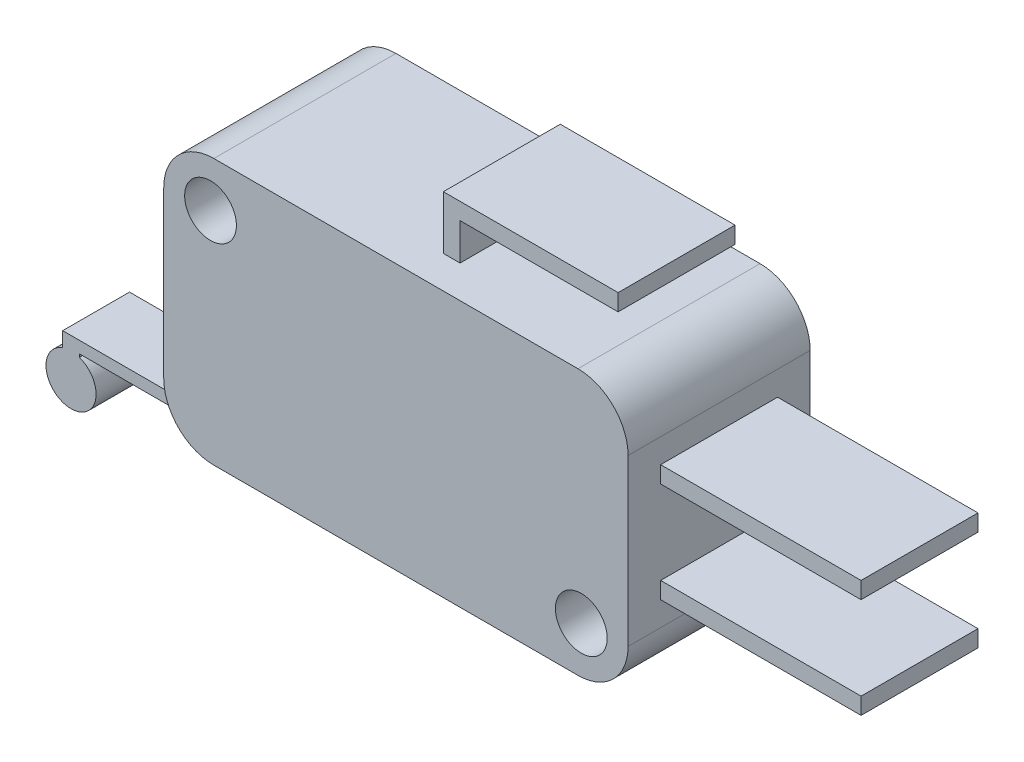
SolidWorks part; units mm, degrees
ref_plane "Front Plane" through (0, 0, 0) normal (0, 0, 1) x (1, 0, 0)
ref_plane "Top Plane" through (0, 0, 0) normal (0, 1, 0) x (1, 0, 0)
ref_plane "Right Plane" through (0, 0, 0) normal (1, 0, 0) x (0, 0, -1)
sketch "Sketch2" plane through (141.8815, 374.1811, -6.1753) normal (0, 0, -1) x (1, 0, 0)
  line L1 (-11.4546, 7.5292) -> (16.3454, 7.5292)
  line L2 (-11.4546, 7.5292) -> (-11.4546, -8.3708)
  line L3 (-11.4546, -8.3708) -> (16.3454, -8.3708)
  line L4 (16.3454, 7.5292) -> (16.3454, -8.3708)
  dimension "D1" = 27.8
  dimension "D2" = 15.9
extrude "Boss-Extrude1" add sketch "Sketch2" along normal mid plane 10.9
fillet "Fillet1" radius 3 4 edges at (158.2268, 382.552, -6.1752) (158.2268, 366.652, -6.1752) (130.4268, 382.552, -6.1754) (130.4268, 366.652, -6.1754)
sketch "Sketch3" plane through (0.0001, 0, -11.6265) normal (0, 0, -1) x (-1, 0, 0)
  line L0 (-144.3268, 366.652) -> (-144.3268, 382.552) construction
  line L1 (-155.2268, 366.652) -> (-133.4268, 366.652) construction
  line L2 (-133.4268, 382.552) -> (-155.2268, 382.552) construction
  circle A0 centre (-155.4268, 369.452) radius 1.55
  circle A1 centre (-133.2268, 379.752) radius 1.55
  dimension "D1" = 3.1
  dimension "D2" = 3.1
  dimension "D3" = 22.2
  dimension "D6" = 10.3
  dimension "D4" = 11.1
  dimension "D5" = 2.8
extrude "Cut-Extrude1" cut sketch "Sketch3" against normal through all
sketch "Sketch4" plane through (141.8815, 374.1811, -6.1753) normal (0, 0, -1) x (1, 0, 0)
  line L0 (16.3454, -5.3708) -> (16.3454, 4.5292) construction
  line L1 (16.3454, 3.0792) -> (28.3454, 3.0792)
  line L2 (16.3454, 3.0792) -> (16.3454, 2.0792)
  line L3 (16.3454, 2.0792) -> (28.3454, 2.0792)
  line L4 (28.3454, 3.0792) -> (28.3454, 2.0792)
  line L5 (-11.4546, -0.4208) -> (36.7883, -0.4208) construction
  line L6 (16.3454, -2.9208) -> (28.3454, -2.9208)
  line L7 (16.3454, -2.9208) -> (16.3454, -3.9208)
  line L8 (16.3454, -3.9208) -> (28.3454, -3.9208)
  line L9 (28.3454, -2.9208) -> (28.3454, -3.9208)
  line L10 (-11.4546, 4.5292) -> (-11.4546, -5.3708) construction
  line L11 (3.3363, -8.3708) -> (3.3363, -11.5708)
  line L12 (-8.4546, -8.3708) -> (13.3454, -8.3708) construction
  line L13 (3.3363, -11.5708) -> (13.7995, -11.5708)
  line L14 (13.7995, -11.5708) -> (13.7995, -10.5708)
  line L15 (13.7995, -10.5708) -> (4.3363, -10.5708)
  line L16 (4.3363, -10.5708) -> (4.3363, -8.3708)
  line L17 (4.3363, -8.3708) -> (3.3363, -8.3708)
  line L18 (13.3454, 7.5292) -> (-8.4546, 7.5292) construction
  dimension "D1" = 1
  dimension "D2" = 1
  dimension "D3" = 2.5
  dimension "D4" = 2.5
  dimension "D5" = 39.8
  dimension "D6" = 39.8
  dimension "D7" = 19.1
  dimension "D8" = 1
  dimension "D9" = 1
extrude "Boss-Extrude2" add sketch "Sketch4" along normal mid plane 7
sketch "Sketch5" plane through (141.8815, 374.1811, -6.1753) normal (0, 0, -1) x (1, 0, 0)
  line L0 (5.1238, 7.5292) -> (5.1238, 8.5292)
  line L1 (13.3454, 7.5292) -> (-8.4546, 7.5292) construction
  line L2 (5.1238, 8.5292) -> (-20.9546, 8.5292)
  line L3 (-20.9546, 8.5292) -> (-20.9546, 9.415)
  line L5 (-19.9546, 9.415) -> (-19.9546, 9.2292)
  line L6 (-19.9546, 9.2292) -> (6.1238, 9.2292)
  line L7 (6.1238, 9.2292) -> (6.1238, 7.5292)
  line L8 (6.1238, 7.5292) -> (5.1238, 7.5292)
  line L9 (-20.4546, 12.3292) -> (-24.7968, 12.3292) construction
  line L10 (-8.4546, -8.3708) -> (13.3454, -8.3708) construction
  arc A0 (-19.9546, 9.415) -> (-20.9546, 9.415) centre (-20.4546, 10.8292) ccw
  circle A1 centre (13.5454, 4.7292) radius 1.55 construction
  dimension "D4" = 34
  dimension "D1" = 1
  dimension "D2" = 0.7
  dimension "D3" = 1
  dimension "D6" = 20.7
extrude "Boss-Extrude3" add sketch "Sketch5" along normal mid plane 4
